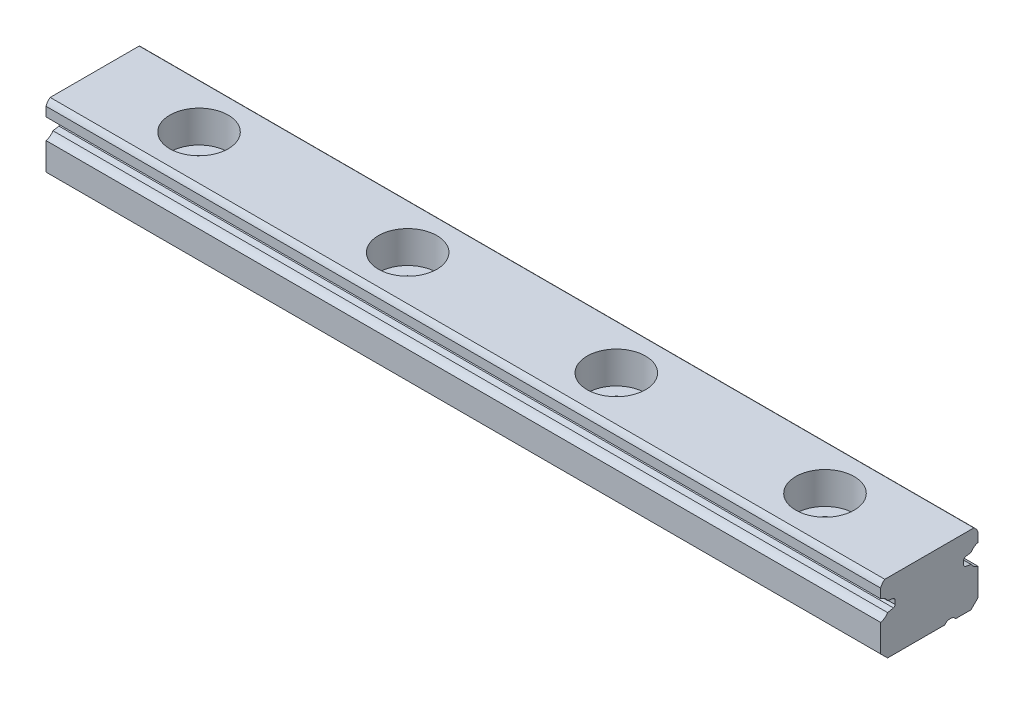
SolidWorks part; units mm, degrees
ref_plane "Front Plane" through (0, 0, 0) normal (0, 0, 1) x (1, 0, 0)
ref_plane "Top Plane" through (0, 0, 0) normal (0, 1, 0) x (1, 0, 0)
ref_plane "Right Plane" through (0, 0, 0) normal (1, 0, 0) x (0, 0, -1)
sketch "Sketch1" plane through (0, 0, 0) normal (1, 0, 0) x (0, 0, -1)
  line L0 (-3.5, 0.5) -> (-3, 0)
  line L1 (-3, 0) -> (3, 0)
  line L2 (3, 0) -> (3.5, 0.5)
  line L3 (3.5, 0.5) -> (3.5, 2.4652)
  line L4 (2.9999, 2.826) -> (2.572, 2.9015)
  line L5 (2.45, 3.051) -> (2.45, 3.349)
  line L6 (2.572, 3.4985) -> (2.9999, 3.574)
  line L7 (3.5, 3.9348) -> (3.5, 4.6)
  line L8 (3.2, 5) -> (-3.2, 5)
  line L9 (-3.5, 4.6) -> (-3.5, 3.9348)
  line L10 (-2.9999, 3.574) -> (-2.572, 3.4985)
  line L11 (-2.45, 3.349) -> (-2.45, 3.051)
  line L12 (-2.572, 2.9015) -> (-2.9999, 2.826)
  line L13 (-3.5, 2.4652) -> (-3.5, 0.5)
  arc A0 (3.5, 2.4652) -> (2.9999, 2.826) centre (3.65, 3.2) cw
  arc A1 (2.572, 2.9015) -> (2.45, 3.051) centre (2.8118, 3.2216) cw
  arc A2 (2.45, 3.349) -> (2.572, 3.4985) centre (2.8118, 3.1784) cw
  arc A3 (2.9999, 3.574) -> (3.5, 3.9348) centre (3.65, 3.2) cw
  arc A4 (3.5, 4.6) -> (3.2, 5) centre (2.7421, 4.344) ccw
  arc A5 (-3.2, 5) -> (-3.5, 4.6) centre (-2.7421, 4.344) ccw
  arc A6 (-3.5, 3.9348) -> (-2.9999, 3.574) centre (-3.65, 3.2) cw
  arc A7 (-2.572, 3.4985) -> (-2.45, 3.349) centre (-2.8118, 3.1784) cw
  arc A8 (-2.45, 3.051) -> (-2.572, 2.9015) centre (-2.8118, 3.2216) cw
  arc A9 (-2.9999, 2.826) -> (-3.5, 2.4652) centre (-3.65, 3.2) cw
extrude "Extrude1" add sketch "Sketch1" along normal blind 60
sketch "Sketch2" plane through (0, 0, 0) normal (0, 0, -1) x (-1, 0, 0)
  line L0 (-7.5, 5) -> (-5.4, 5)
  line L1 (-5.4, 5) -> (-5.4, 2.7)
  line L2 (-5.4, 2.7) -> (-6.3, 2.7)
  line L3 (-6.3, 2.7) -> (-6.3, 0.2)
  line L4 (-6.3, 0.2) -> (-6.1, 0)
  line L5 (-6.1, 0) -> (-7.5, 0)
  line L6 (-60, 5) -> (0, 5) construction
  line L7 (-7.5, 0) -> (-7.5, 5) construction
  line L8 (-60, 0) -> (0, 0) construction
  line L9 (0, 2.4652) -> (0, 0.5) construction
  line L10 (-7.5, 5) -> (-7.5, 0)
  dimension "D1" = 7.5
  dimension "D2" = 2.4
  dimension "D3" = 2.8
  dimension "D4" = 4.2
  dimension "D5" = 2.3
  dimension "D6" = 45
revolve "Cut-Revolve1" cut sketch "Sketch2" angle 360 about L7 reverse direction yes
sketch "Sketch3" plane through (45, 0, 0) normal (0, 0, -1) x (-1, 0, 0)
  line L0 (-7.5, 5) -> (-5.4, 5)
  line L1 (-5.4, 5) -> (-5.4, 2.7)
  line L2 (-5.4, 2.7) -> (-6.3, 2.7)
  line L3 (-6.3, 2.7) -> (-6.3, 0.2)
  line L4 (-6.3, 0.2) -> (-6.1, 0)
  line L5 (-6.1, 0) -> (-7.5, 0)
  line L6 (-15, 0) -> (45, 0) construction
  line L7 (-7.5, 0) -> (-7.5, 5) construction
  line L8 (-15, 5) -> (45, 5) construction
  line L9 (-15, 2.4652) -> (-15, 0.5) construction
  line L10 (-7.5, 5) -> (-7.5, 0)
  dimension "D1" = 7.5
  dimension "D2" = 2.4
  dimension "D3" = 2.8
  dimension "D4" = 45
  dimension "D5" = 4.2
  dimension "D6" = 2.3
revolve "Cut-Revolve2" cut sketch "Sketch3" angle 360 about L7 reverse direction yes
sketch "Sketch6" plane through (0, 0, 0) normal (1, 0, 0) x (0, 0, -1)
  circle A0 centre (1.5, -0.3) radius 0.5
extrude "Extrude2" cut sketch "Sketch6" along normal through all
ref_axis "Axis1" through (-3, 0, 0) along (1, 0, 0)
pattern_linear "LPattern1" count 3 spacing 15 along (-1, 0, 0) of "Cut-Revolve2"
